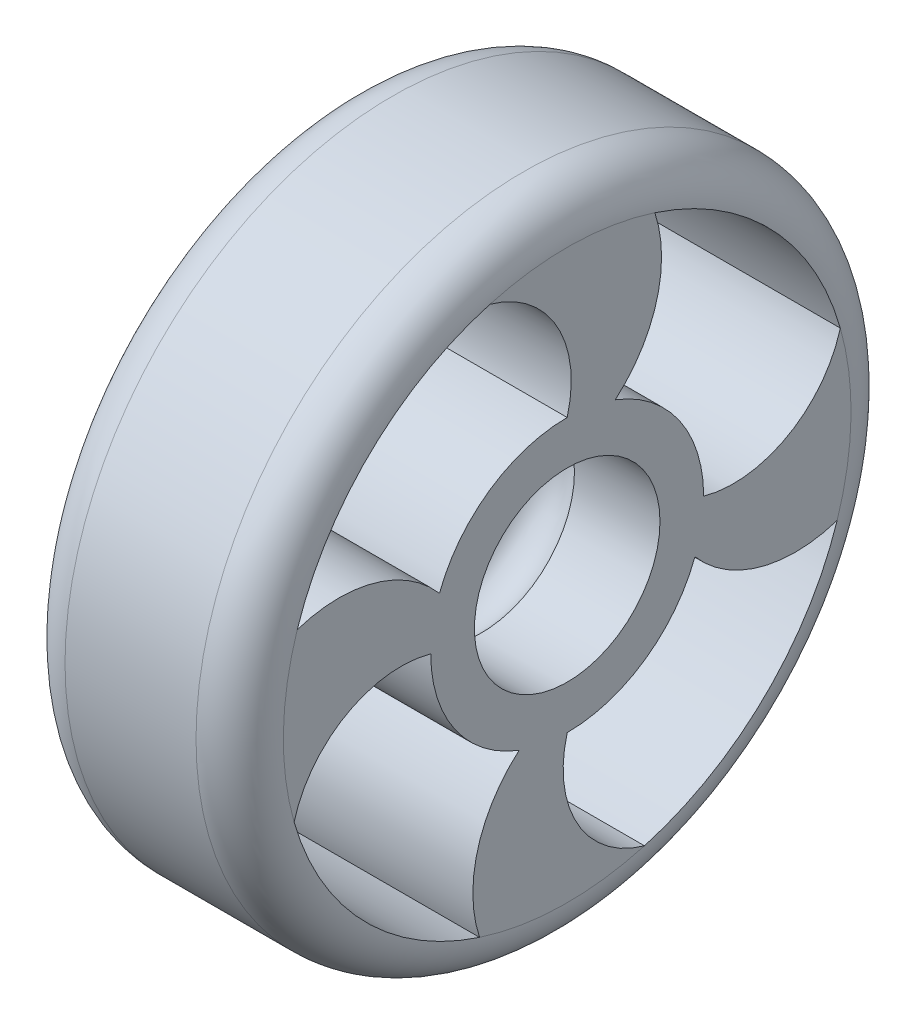
SolidWorks part; units mm, degrees
ref_plane "Front Plane" through (0, 0, 0) normal (0, 0, 1) x (1, 0, 0)
ref_plane "Top Plane" through (0, 0, 0) normal (0, 1, 0) x (1, 0, 0)
ref_plane "Right Plane" through (0, 0, 0) normal (1, 0, 0) x (0, 0, -1)
sketch "Sketch1" plane through (0, 0, 0) normal (1, 0, 0) x (0, 0, -1)
  circle A0 centre (0, 0) radius 10.795
  circle A1 centre (0, 0) radius 15.875
  dimension "D1" = 5.08
extrude "Boss-Extrude1" add sketch "Sketch1" along normal blind 25.4
sketch "Sketch2" plane through (0, 0, 0) normal (-1, 0, 0) x (0, 0, 1)
  arc A0 (15.875, 0) -> (14.8593, 5.5872) centre (0, 0) ccw
  arc A1 (15.875, 0) -> (31.7723, -8.9911) centre (19.3281, -12.4442) cw
  circle A2 centre (0, 0) radius 38.1
  arc A3 (-31.407, -10.1943) -> (-8.9911, -31.7723) centre (0, 0) ccw
  arc A4 (14.8593, 5.5872) -> (31.407, 10.1943) centre (26.5615, -4.4234) cw
  arc A5 (5.5872, -14.8593) -> (10.1943, -31.407) centre (-4.4234, -26.5615) cw
  arc A6 (0, -15.875) -> (-8.9911, -31.7723) centre (-12.4442, -19.3281) cw
  arc A7 (0, -15.875) -> (5.5872, -14.8593) centre (0, 0) ccw
  arc A8 (-14.8593, -5.5872) -> (-31.407, -10.1943) centre (-26.5615, 4.4234) cw
  arc A9 (-15.875, 0) -> (-31.7723, 8.9911) centre (-19.3281, 12.4442) cw
  arc A10 (-15.875, 0) -> (-14.8593, -5.5872) centre (0, 0) ccw
  arc A11 (-5.5872, 14.8593) -> (-10.1943, 31.407) centre (4.4234, 26.5615) cw
  arc A12 (0, 15.875) -> (8.9911, 31.7723) centre (12.4442, 19.3281) cw
  arc A13 (0, 15.875) -> (-5.5872, 14.8593) centre (0, 0) ccw
  arc A14 (-10.1943, 31.407) -> (-31.7723, 8.9911) centre (0, 0) ccw
  circle A15 centre (0, 0) radius 33.02 construction
  arc A16 (31.407, 10.1943) -> (8.9911, 31.7723) centre (0, 0) ccw
  arc A17 (10.1943, -31.407) -> (31.7723, -8.9911) centre (0, 0) ccw
  point P1 (33.02, 0)
  point P32 (0, 0)
  dimension "D1" = 5.08
  dimension "D2" = 4
extrude "Boss-Extrude2" add sketch "Sketch2" against normal blind 25.4
sketch "Sketch5" plane through (0, 0, 0) normal (0, 0, 1) x (1, 0, 0)
  line L5 (15.4503, 10.7938) -> (9.9497, 10.7938)
  arc A0 (15.4503, 10.7938) -> (9.9497, 10.7938) centre (12.7, 9.2075) ccw
sweep "Cut-Sweep1" cut profiles "Sketch5" path edge at (25.4, 0, -10.795)
fillet "Fillet1" radius 5.08 2 edges at (25.4, 0, 38.1) (0, 0, 38.1)
